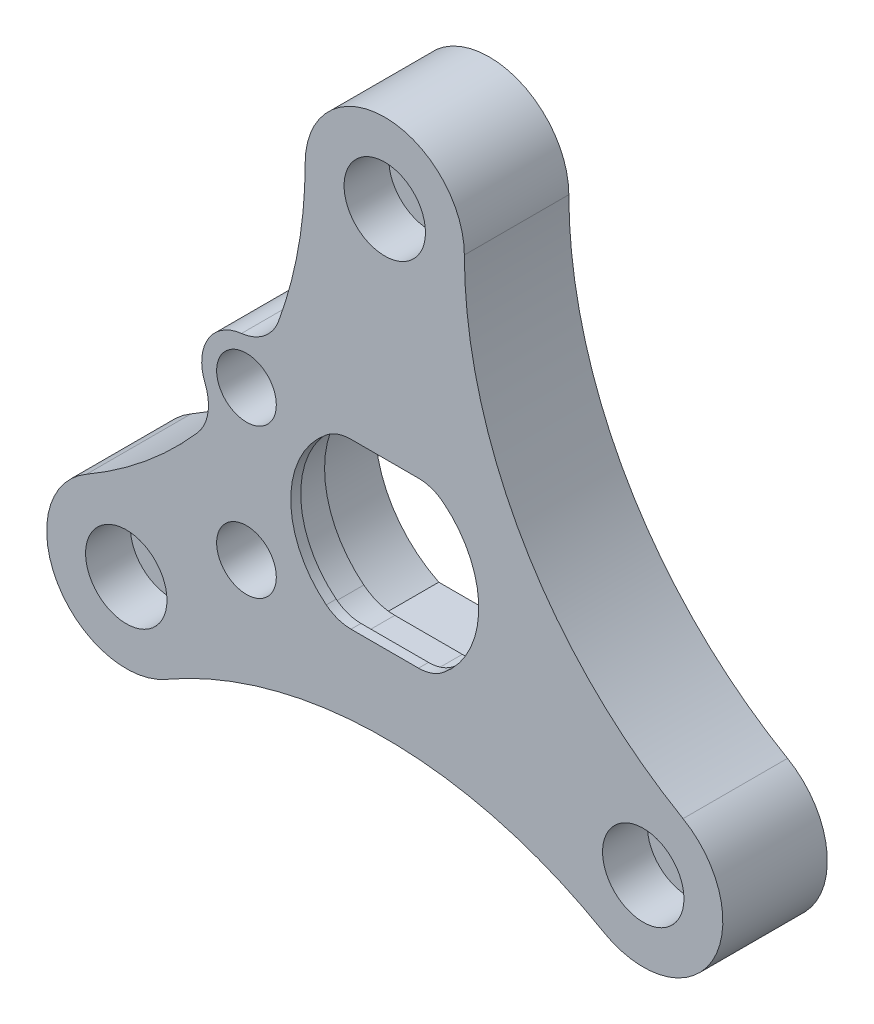
SolidWorks part; units mm, degrees
ref_plane "Front Plane" through (0, 0, 0) normal (0, 0, 1) x (1, 0, 0)
ref_plane "Top Plane" through (0, 0, 0) normal (0, 1, 0) x (1, 0, 0)
ref_plane "Right Plane" through (0, 0, 0) normal (1, 0, 0) x (0, 0, -1)
sketch "Sketch1" plane through (0, 0, 0) normal (0, 0, 1) x (1, 0, 0)
  line L0 (0, 67.3162) -> (0, 0) construction
  line L1 (0, -2.75) -> (0, 2.75) construction
  line L2 (0, 0) -> (58.2975, -33.6581) construction
  line L3 (0, 0) -> (-58.2975, -33.6581) construction
  line L4 (-29.9808, -8.0718) -> (-21.9808, -21.9282) construction
  line L6 (4.8335, 9.265) -> (-4.8335, 9.265)
  line L10 (4.8335, -9.265) -> (-4.8335, -9.265)
  line L11 (3.3, 0) -> (-3.3, 0) construction
  circle A0 centre (0, 0) radius 30 construction
  circle A1 centre (0, 30) radius 4.09
  circle A2 centre (25.9808, -15) radius 4.09
  circle A3 centre (-25.9808, -15) radius 4.09
  arc A4 (-21.9808, -21.9282) -> (-29.9808, -8.0718) centre (-25.9808, -15) cw
  arc A5 (29.9808, -8.0718) -> (21.9808, -21.9282) centre (25.9808, -15) cw
  arc A6 (-8, 30) -> (8, 30) centre (0, 30) cw
  arc A7 (-8, 30) -> (-29.9808, -8.0718) centre (-51.9615, 30) cw
  arc A8 (8, 30) -> (29.9808, -8.0718) centre (51.9615, 30) ccw
  arc A9 (21.9808, -21.9282) -> (-21.9808, -21.9282) centre (0, -60) ccw
  circle A12 centre (0, 30) radius 2
  circle A13 centre (25.9808, -15) radius 2
  circle A14 centre (-25.9808, -15) radius 2
  arc A17 (4.8335, 9.265) -> (4.8335, -9.265) centre (0, 0) cw
  arc A18 (-4.8335, 9.265) -> (-4.8335, -9.265) centre (0, 0) ccw
  point P26 (-25.9808, -15)
  point P28 (-10.45, 0)
  dimension "D1" = 60
  dimension "D4" = 8.18
  dimension "D5" = 8
  dimension "D6" = 4
  dimension "D7" = 10.45
  dimension "D2" = 120
  dimension "D3" = 120
  dimension "D8" = 18.53
extrude "Boss-Extrude1" add sketch "Sketch1" along normal blind 4.5 contours A9 A5 A8 A6 A7 A4 A3 A2 A1 region at (-32.1181, -18.5434, 0)
extrude "Boss-Extrude2" add sketch "Sketch1<3>" against normal blind 6 contours A9 A5 A8 A6 A7 A4 A3 A2 A1 | A1 A12 | A2 A13 | A3 A14 region at (-3.9743, 30, 0) region at (22.0064, -15, 0) region at (-29.9551, -15, 0) region at (-32.1181, -18.5434, 0)
sketch "Sketch1<3>" plane through (0, 0, 0) normal (0, 0, 1) x (1, 0, 0) same geometry as "Sketch1"
sketch "Sketch2" plane through (0, 0, 4.5) normal (0, 0, 1) x (1, 0, 0)
  line L0 (-4.5817, 8.265) -> (4.5817, 8.265)
  line L1 (-4.5817, -8.265) -> (4.5817, -8.265)
  line L2 (4.8335, 9.265) -> (-4.8335, 9.265) construction
  line L4 (4.8335, -9.265) -> (-4.8335, -9.265) construction
  line L5 (-10.45, 9.265) -> (10.45, 9.265)
  line L6 (-10.45, 9.265) -> (-10.45, -9.265)
  line L7 (-10.45, -9.265) -> (10.45, -9.265)
  line L8 (10.45, 9.265) -> (10.45, -9.265)
  arc A0 (4.5817, 8.265) -> (4.5817, -8.265) centre (0, 0) cw
  arc A1 (-4.5817, 8.265) -> (-4.5817, -8.265) centre (0, 0) ccw
  arc A2 (4.8335, -9.265) -> (4.8335, 9.265) centre (0, 0) ccw construction
  arc A3 (-4.8335, 9.265) -> (-4.8335, -9.265) centre (0, 0) ccw construction
  point P20 (-10.45, 0)
  dimension "D2" = 1
  dimension "D1" = 1
extrude "Boss-Extrude3" add sketch "Sketch2" against normal blind 1
fillet "Fillet1" radius 5 4 edges at (-4.8335, -9.265, -1.25) (4.8335, -9.265, -1.25) (-4.8335, 9.265, -1.25) (4.8335, 9.265, -1.25)
fillet "Fillet2" radius 4 4 edges at (-4.5817, 8.265, 4) (4.5817, 8.265, 4) (-4.5817, -8.265, 4) (4.5817, -8.265, 4)
sketch "Sketch3" plane through (0, 0, -6) normal (0, 0, -1) x (-1, 0, 0)
  line L0 (-38.4, -7.5) -> (13.9, -7.5) construction
  line L1 (-23.95, -39.7) -> (-23.95, -7.5) construction
  line L2 (13.9, -7.5) -> (38.4, -7.5) construction
  line L3 (-38.4, -39.7) -> (38.4, -39.7) construction
  line L4 (0, 2.75) -> (0, -2.75) construction
  line L5 (13.9, 7.5) -> (13.9, -7.5) construction
  line L6 (-38.4, 17.5) -> (38.4, 17.5) construction
  line L7 (-38.4, 17.5) -> (-38.4, -17.5) construction
  line L8 (-38.4, -17.5) -> (38.4, -17.5) construction
  line L9 (38.4, 17.5) -> (38.4, -17.5) construction
  line L10 (5.775, 0) -> (-5.775, 0) construction
  circle A0 centre (13.9, 7.5) radius 1.75
  circle A1 centre (13.9, -7.5) radius 1.75
  circle A2 centre (13.9, 7.5) radius 4.5
  point P12 (0, -39.7)
  point P17 (13.9, 0)
  dimension "D2" = 3.5
  dimension "D10" = 9
  dimension "D1" = 15
  dimension "D3" = 32.2
  dimension "D4" = 52.3
  dimension "D5" = 28.9
  dimension "D6" = 24.5
  dimension "D7" = 35
  dimension "D8" = 76.8
  dimension "D9" = 10
extrude "Boss-Extrude4" add sketch "Sketch3<3>" against normal up to surface (10.5 mm away) contours A2 up to face at (0, 0, 4.5)
sketch "Sketch3<3>" plane through (0, 0, -6) normal (0, 0, -1) x (-1, 0, 0) same geometry as "Sketch3"
extrude "Cut-Extrude1" cut sketch "Sketch3" against normal through all contours A0 | A1
fillet "Fillet3" radius 4.5 2 edges at (-12.0375, 11.5965, -0.75) (-16.5912, 3.8934, -0.75)
sketch "Sketch4" plane through (0, 0, -6) normal (0, 0, -1) x (-1, 0, 0)
  line L0 (-5.0727, 10.265) -> (5.0727, 10.265)
  line L1 (5.0727, -10.265) -> (-5.0727, -10.265)
  line L2 (-3.393, 9.265) -> (3.393, 9.265) construction
  line L4 (8.083, 13.265) -> (-8.083, 13.265)
  arc A0 (-5.0727, 10.265) -> (-5.0727, -10.265) centre (0, 0) ccw
  arc A1 (5.0727, 10.265) -> (5.0727, -10.265) centre (0, 0) cw
  arc A2 (-6.5058, 8.1778) -> (-6.5058, -8.1778) centre (0, 0) ccw construction
  arc A3 (-5, 30) -> (5, 30) centre (0, 30) ccw
  arc A4 (-28.4808, -10.6699) -> (-23.4808, -19.3301) centre (-25.9808, -15) cw
  arc A5 (-14.3223, 1.9166) -> (-5.5013, -13.3618) centre (0, 0) ccw
  arc A6 (-23.4808, -19.3301) -> (-5.5013, -13.3618) centre (0, -60) cw
  arc A7 (-28.4808, -10.6699) -> (-14.3223, 1.9166) centre (-51.9615, 30) ccw
  arc A8 (21.9808, -21.9282) -> (-21.9808, -21.9282) centre (0, -60) ccw construction
  arc A9 (-29.9808, -8.0718) -> (-8, 30) centre (-51.9615, 30) ccw construction
  circle A10 centre (-25.9808, -15) radius 2 construction
  arc A11 (-5, 30) -> (-8.083, 13.265) centre (-51.9615, 30) cw
  arc A12 (5, 30) -> (8.083, 13.265) centre (51.9615, 30) ccw
  circle A13 centre (0, 30) radius 2 construction
  arc A14 (8, 30) -> (10.6753, 14.8983) centre (51.9615, 30) ccw construction
  arc A15 (28.4808, -10.6699) -> (23.4808, -19.3301) centre (25.9808, -15) ccw
  arc A17 (18.8883, -3.3398) -> (28.4808, -10.6699) centre (51.9615, 30) ccw
  arc A18 (11.113, -14.3723) -> (23.4808, -19.3301) centre (0, -60) cw
  circle A19 centre (25.9808, -15) radius 2 construction
  arc A20 (18.8883, -3.3398) -> (11.113, -14.3723) centre (10.1333, -5.4258) cw
  arc A22 (18.8273, 1.1082) -> (29.9808, -8.0718) centre (51.9615, 30) ccw construction
  circle A23 centre (13.9, -7.5) radius 1.75 construction
  point P49 (17.4899, -10.6104)
  dimension "D2" = 1
  dimension "D3" = 3
  dimension "D4" = 3
  dimension "D5" = 3
  dimension "D6" = 3
  dimension "D7" = 3
  dimension "D9" = 3
  dimension "D10" = 3
  dimension "D11" = 3
  dimension "D12" = 3
  dimension "D13" = 3
  dimension "D14" = 4.75
  dimension "D15" = 9
  dimension "D1" = 1
  dimension "D8" = 3
  dimension "D16" = 4.3
extrude "Cut-Extrude2" cut sketch "Sketch4" against normal blind 6.1
sketch "Sketch5" plane through (0, 0, 4.5) normal (0, 0, 1) x (1, 0, 0)
  circle A0 centre (-13.9, 7.5) radius 3
  circle A1 centre (-13.9, -7.5) radius 3
  dimension "D1" = 6
extrude "Cut-Extrude3" cut sketch "Sketch5" against normal blind 4.5
fillet "Fillet4" radius 1 12 edges at (8.083, 13.265, -2.95) (-8.083, 13.265, -2.95) (5.5013, -13.3618, -2.95) (14.3223, 1.9166, -2.95) (-11.113, -14.3723, -2.95) (-18.8883, -3.3398, -2.95) (-23.4808, -19.3301, -2.95) (-28.4808, -10.6699, -2.95) (23.4808, -19.3301, -2.95) (28.4808, -10.6699, -2.95) (5, 30, -2.95) (-5, 30, -2.95)
sketch "Sketch6" plane through (0, 0, -6) normal (0, 0, 1) x (1, 0, 0)
  line L0 (16.642, 3.8247) -> (26.1682, -1.6753)
  line L1 (16.642, 3.8247) -> (5.0087, -16.3247)
  line L2 (26.1682, -1.6753) -> (14.5349, -21.8247)
  line L3 (5.0087, -16.3247) -> (14.5349, -21.8247)
  line L4 (5.775, 0) -> (-5.775, 0) construction
  arc A0 (8, 30) -> (29.9808, -8.0718) centre (51.9615, 30) ccw construction
  arc A1 (21.9808, -21.9282) -> (-21.9808, -21.9282) centre (0, -60) ccw construction
  dimension "D1" = 11
  dimension "D3" = 60
  dimension "D4" = 12.5
extrude "Cut-Extrude4" [suppressed] cut sketch "Sketch6" along normal up to surface (6.1 mm away)
fillet "Fillet5" [suppressed] radius 1.5
fillet "Fillet6" [suppressed] radius 3
fillet "Fillet7" [suppressed] radius 1
